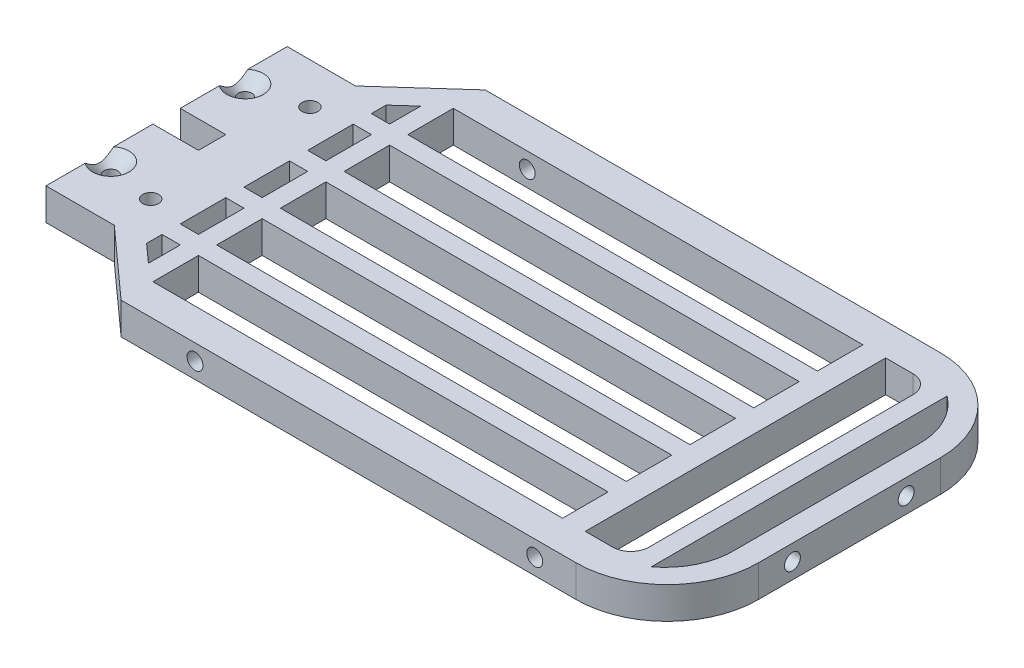
SolidWorks part; units mm, degrees
ref_plane "Ön Düzlem" through (0, 0, 0) normal (0, 0, 1) x (1, 0, 0)
ref_plane "Üst Düzlem" through (0, 0, 0) normal (0, 1, 0) x (1, 0, 0)
ref_plane "Sağ Düzlem" through (0, 0, 0) normal (1, 0, 0) x (0, 0, -1)
sketch "Çizim1" plane through (0, 0, 0) normal (0, 1, 0) x (1, 0, 0)
  line L0 (0, 0) -> (0, 53)
  line L1 (0, 53) -> (15, 53)
  line L2 (15, 53) -> (30, 66.5)
  line L3 (30, 66.5) -> (150, 66.5)
  line L4 (150, 66.5) -> (150, -13.5)
  line L5 (150, -13.5) -> (30, -13.5)
  line L6 (30, -13.5) -> (15, 0)
  line L7 (15, 0) -> (0, 0)
  line L8 (0, 26.5) -> (214.08, 26.5) construction
  dimension "D1" = 53
  dimension "D2" = 150
  dimension "D3" = 15
  dimension "D4" = 15
  dimension "D5" = 80
  dimension "D6" = 15
extrude "Yükseklik-Ekstrüzyon1" add sketch "Çizim1" along normal blind 7
sketch "Çizim2" plane through (0, 7, 0) normal (0, 1, 0) x (1, 0, 0)
  line L0 (2.5, 53) -> (2.5, -2.7433) construction
  line L1 (15, 53) -> (0, 53) construction
  line L2 (0, 53) -> (0, 0) construction
  line L3 (0, 26.5) -> (35.1734, 26.5) construction
  circle A0 centre (2.5, 41.25) radius 1.5
  circle A1 centre (2.5, 11.75) radius 1.5
  dimension "D2" = 3
  dimension "D3" = 3
  dimension "D1" = 2.5
  dimension "D4" = 29.5
extrude "Kes-Ekstrüzyon1" cut sketch "Çizim2" against normal blind 7
chamfer "Pah1" distance 2.5 angle 45 2 edges at (2.5, 7, -10.25) (2.5, 7, -39.75)
sketch "Çizim3" plane through (0, 0, 13.5) normal (0, 0, 1) x (1, 0, 0)
  line L0 (30, 3.5) -> (160.3071, 3.5) construction
  line L1 (30, 7) -> (30, 0) construction
  line L2 (0, 7) -> (0, 0) construction
  circle A0 centre (46.24, 3.5) radius 1.75
  dimension "D1" = 3.5
  dimension "D2" = 46.24
extrude "Kes-Ekstrüzyon2" cut sketch "Çizim3" against normal blind 10
sketch "Çizim4" plane through (0, 0, -66.5) normal (0, 0, -1) x (-1, 0, 0)
  line L0 (-30, 3.5) -> (-173.4144, 3.5) construction
  line L1 (-30, 7) -> (-30, 0) construction
  line L2 (0, 7) -> (0, 0) construction
  circle A0 centre (-46.24, 3.5) radius 1.75
  point P8 (0, 3.5)
  dimension "D1" = 3.5
  dimension "D2" = 46.24
extrude "Kes-Ekstrüzyon3" cut sketch "Çizim4" against normal blind 10
fillet "Radyus1" radius 20 2 edges at (150, 3.5, 13.5) (150, 3.5, -66.5)
sketch "Çizim5" plane through (0, 7, 0) normal (0, 1, 0) x (1, 0, 0)
  line L0 (30, -13.5) -> (30, 82.5573) construction
  line L1 (30, -6.5) -> (120, -6.5)
  line L2 (30, -6.5) -> (30, 3.5)
  line L3 (30, 3.5) -> (120, 3.5)
  line L4 (120, -6.5) -> (120, 3.5)
  line L5 (30, 21.5) -> (120, 21.5)
  line L6 (30, 21.5) -> (30, 31.5)
  line L7 (30, 31.5) -> (120, 31.5)
  line L8 (120, 21.5) -> (120, 31.5)
  line L9 (30, 35.5) -> (120, 35.5)
  line L10 (30, 35.5) -> (30, 45.5)
  line L11 (30, 45.5) -> (120, 45.5)
  line L12 (120, 35.5) -> (120, 45.5)
  line L13 (30, 49.5) -> (120, 49.5)
  line L14 (30, 49.5) -> (30, 59.5)
  line L15 (30, 59.5) -> (120, 59.5)
  line L16 (120, 49.5) -> (120, 59.5)
  line L18 (130, 66.5) -> (30, 66.5) construction
  line L20 (120, 17.5) -> (30, 17.5)
  line L21 (120, 17.5) -> (120, 7.5)
  line L22 (120, 7.5) -> (30, 7.5)
  line L23 (30, 17.5) -> (30, 7.5)
  line L25 (125, -6.5) -> (135, -6.5)
  line L26 (125, -6.5) -> (125, 59.5)
  line L27 (125, 59.5) -> (135, 59.5)
  line L28 (135, -6.5) -> (135, 59.5)
  dimension "D1" = 10
  dimension "D2" = 10
  dimension "D3" = 10
  dimension "D4" = 10
  dimension "D5" = 4
  dimension "D6" = 7
  dimension "D7" = 90
  dimension "D8" = 4
  dimension "D9" = 4
  dimension "D10" = 10
  dimension "D11" = 4
  dimension "D12" = 5
  dimension "D13" = 10
extrude "Kes-Ekstrüzyon4" cut sketch "Çizim5" against normal blind 10
fillet "Radyus2" radius 4 2 edges at (135, 3.5, -59.5) (135, 3.5, 6.5)
sketch "Çizim6" plane through (0, 7, 0) normal (0, 1, 0) x (1, 0, 0)
  line L0 (139, -6) -> (139, 59)
  line L1 (145, 6.5) -> (145, 46.5)
  line L3 (150, 6.5) -> (150, 46.5) construction
  line L4 (135, -2.5) -> (135, 55.5) construction
  line L5 (150, 26.5) -> (128.177, 26.5) construction
  arc A0 (139, -6) -> (145, 6.5) centre (130.0081, 6.0061) ccw
  arc A1 (145, 46.5) -> (139, 59) centre (130.0081, 46.9939) ccw
  dimension "D4" = 15
  dimension "D5" = 15
  dimension "D1" = 5
  dimension "D2" = 4
  dimension "D3" = 65
extrude "Kes-Ekstrüzyon5" cut sketch "Çizim6" against normal blind 10
sketch "Çizim7" plane through (150, 0, 0) normal (1, 0, 0) x (0, 0, -1)
  line L0 (6.5, 3.5) -> (46.5, 3.5) construction
  line L1 (6.5, 7) -> (6.5, 0) construction
  line L2 (46.5, 0) -> (46.5, 7) construction
  line L3 (26.5, 7) -> (26.5, 0) construction
  line L4 (6.5, 7) -> (46.5, 7) construction
  line L5 (6.5, 0) -> (46.5, 0) construction
  circle A0 centre (14, 3.5) radius 1.75
  circle A1 centre (39, 3.5) radius 1.75
  dimension "D2" = 3.5
  dimension "D3" = 3.5
  dimension "D1" = 25
extrude "Kes-Ekstrüzyon6" cut sketch "Çizim7" against normal blind 7
sketch "Çizim8" plane through (0, 7, 0) normal (0, 1, 0) x (1, 0, 0)
  line L0 (0, 26.5) -> (17.6304, 26.5) construction
  line L1 (0, 38.1275) -> (0, 14.8725) construction
  line L3 (10, 29.5) -> (0, 29.5)
  line L4 (10, 29.5) -> (10, 23.5)
  line L5 (10, 23.5) -> (0, 23.5)
  line L6 (0, 29.5) -> (0, 23.5)
  dimension "D1" = 6
  dimension "D2" = 10
extrude "Kes-Ekstrüzyon7" cut sketch "Çizim8" against normal blind 10
sketch "Çizim9" plane through (0, 7, 0) normal (0, 1, 0) x (1, 0, 0)
  line L0 (14, 70.1375) -> (14, -17.3124) construction
  line L1 (0, 53) -> (0, 44.3725) construction
  line L2 (10, 26.5) -> (46.0629, 26.5) construction
  line L3 (10, 23.5) -> (10, 29.5) construction
  circle A0 centre (14, 44) radius 1.75
  circle A1 centre (14, 9) radius 1.75
  point P4 (0, 48.6862)
  dimension "D2" = 3.5
  dimension "D3" = 35
  dimension "D1" = 14
extrude "Kes-Ekstrüzyon8" cut sketch "Çizim9" against normal blind 10
sketch "Çizim10" plane through (0, 0, 13.5) normal (0, 0, 1) x (1, 0, 0)
  line L0 (130, 3.5) -> (85.8813, 3.5) construction
  line L1 (130, 0) -> (130, 7) construction
  circle A0 centre (120.89, 3.5) radius 1.75
  dimension "D1" = 3.5
  dimension "D2" = 9.11
extrude "Kes-Ekstrüzyon9" cut sketch "Çizim10" against normal blind 6
sketch "Çizim11" plane through (0, 0, -66.5) normal (0, 0, -1) x (-1, 0, 0)
  line L0 (-130, 3.5) -> (-82.5806, 3.5) construction
  line L1 (-130, 7) -> (-130, 0) construction
  circle A0 centre (-120.89, 3.5) radius 1.75
  dimension "D1" = 3.5
  dimension "D2" = 9.11
extrude "Kes-Ekstrüzyon10" cut sketch "Çizim11" against normal blind 6
sketch "Çizim12" plane through (0, 7, 0) normal (0, 1, 0) x (1, 0, 0)
  line L1 (130, 66.5) -> (30, 66.5) construction
  line L2 (26, 56.3319) -> (26, 49.5)
  line L3 (30, -13.5) -> (130, -13.5) construction
  line L4 (22, 52.7319) -> (22, 49.5)
  line L5 (30, 45.5) -> (30, 35.5) construction
  line L9 (26, 56.3319) -> (22, 52.7319)
  line L10 (26, -3.5) -> (22, 0.1)
  line L13 (15, 0) -> (30, -13.5) construction
  line L14 (30, 66.5) -> (15, 53) construction
  line L15 (26, 35.5) -> (22, 35.5)
  line L16 (26, 31.5) -> (22, 31.5)
  line L17 (26, 45.5) -> (22, 45.5)
  line L18 (26, 49.5) -> (22, 49.5)
  line L19 (26, 21.5) -> (22, 21.5)
  line L20 (26, 17.5) -> (22, 17.5)
  line L21 (26, 7.5) -> (22, 7.5)
  line L22 (26, 3.5) -> (22, 3.5)
  line L23 (120, 3.5) -> (30, 3.5) construction
  line L24 (30, 7.5) -> (120, 7.5) construction
  line L25 (120, 17.5) -> (30, 17.5) construction
  line L26 (30, 21.5) -> (120, 21.5) construction
  line L27 (120, 31.5) -> (30, 31.5) construction
  line L28 (30, 35.5) -> (120, 35.5) construction
  line L29 (120, 45.5) -> (30, 45.5) construction
  line L30 (30, 49.5) -> (120, 49.5) construction
  line L31 (22, 45.5) -> (22, 35.5)
  line L32 (26, 45.5) -> (26, 35.5)
  line L33 (26, 31.5) -> (26, 21.5)
  line L34 (22, 31.5) -> (22, 21.5)
  line L35 (26, 17.5) -> (26, 7.5)
  line L36 (22, 17.5) -> (22, 7.5)
  line L37 (26, 3.5) -> (26, -3.5)
  line L38 (22, 3.5) -> (22, 0.1)
  dimension "D1" = 4
  dimension "D2" = 4
  dimension "D3" = 10.1681
  dimension "D4" = 10
extrude "Kes-Ekstrüzyon11" cut sketch "Çizim12" against normal blind 10
